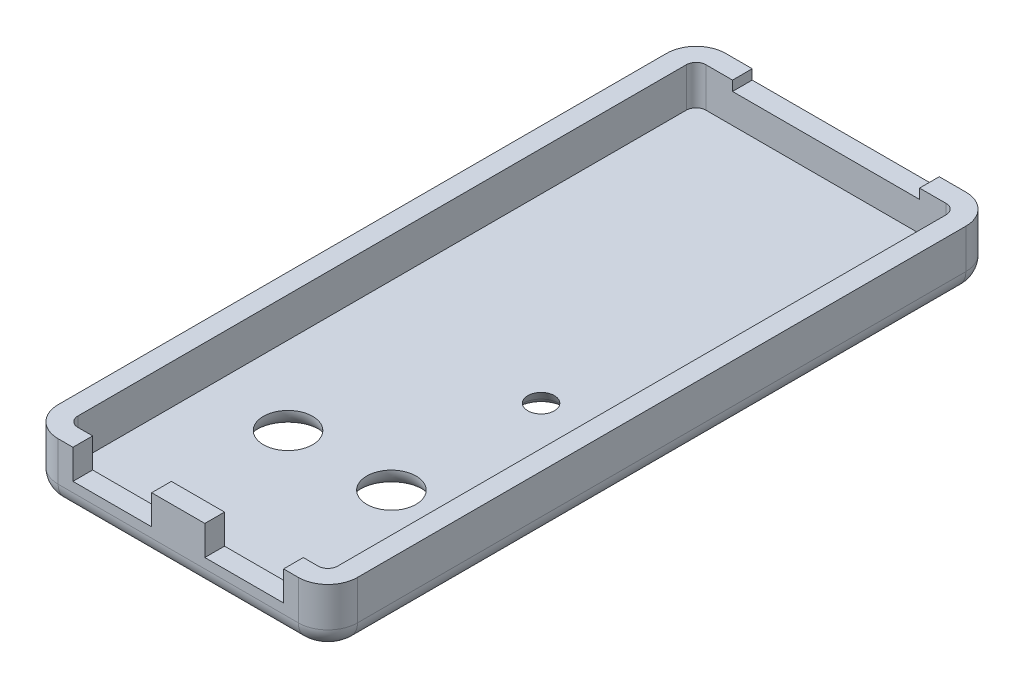
SolidWorks part; units mm, degrees
ref_plane "Front Plane" through (0, 0, 0) normal (0, 0, 1) x (1, 0, 0)
ref_plane "Top Plane" through (0, 0, 0) normal (0, 1, 0) x (1, 0, 0)
ref_plane "Right Plane" through (0, 0, 0) normal (1, 0, 0) x (0, 0, -1)
sketch "Sketch1" plane through (0, 0, 0) normal (0, 1, 0) x (1, 0, 0)
  line L1 (-12.2, 33.9) -> (12.2, 33.9)
  line L2 (-15.2, 30.9) -> (-15.2, -30.9)
  line L3 (-12.2, -33.9) -> (12.2, -33.9)
  line L4 (15.2, 30.9) -> (15.2, -30.9)
  line L5 (-15.2, 33.9) -> (15.2, -33.9) construction
  line L6 (-15.2, -33.9) -> (15.2, 33.9) construction
  arc A0 (-15.2, -30.9) -> (-12.2, -33.9) centre (-12.2, -30.9) ccw
  arc A1 (12.2, -33.9) -> (15.2, -30.9) centre (12.2, -30.9) ccw
  arc A2 (12.2, 33.9) -> (15.2, 30.9) centre (12.2, 30.9) cw
  arc A3 (-12.2, 33.9) -> (-15.2, 30.9) centre (-12.2, 30.9) ccw
  point P0 (0, 0)
  dimension "D3" = 3
  dimension "D1" = 67.8
  dimension "D2" = 30.4
extrude "Boss-Extrude1" add sketch "Sketch1" along normal blind 2
sketch "Sketch2" plane through (0, 2, 0) normal (0, 1, 0) x (1, 0, 0)
  line L0 (-12.2, -31.9) -> (12.2, -31.9)
  line L1 (13.2, -30.9) -> (13.2, 30.9)
  line L2 (12.2, 31.9) -> (-12.2, 31.9)
  line L3 (-13.2, 30.9) -> (-13.2, -30.9)
  line L4 (-12.2, -33.9) -> (12.2, -33.9)
  line L5 (15.2, -30.9) -> (15.2, 30.9)
  line L6 (12.2, 33.9) -> (-12.2, 33.9)
  line L7 (-15.2, 30.9) -> (-15.2, -30.9)
  line L8 (-12.2, -33.9) -> (12.2, -33.9)
  line L9 (15.2, -30.9) -> (15.2, 30.9)
  line L10 (12.2, 33.9) -> (-12.2, 33.9)
  line L11 (-15.2, 30.9) -> (-15.2, -30.9)
  arc A0 (-13.2, -30.9) -> (-12.2, -31.9) centre (-12.2, -30.9) ccw
  arc A1 (12.2, -31.9) -> (13.2, -30.9) centre (12.2, -30.9) ccw
  arc A2 (13.2, 30.9) -> (12.2, 31.9) centre (12.2, 30.9) ccw
  arc A3 (-12.2, 31.9) -> (-13.2, 30.9) centre (-12.2, 30.9) ccw
  arc A4 (-15.2, -30.9) -> (-12.2, -33.9) centre (-12.2, -30.9) ccw
  arc A5 (12.2, -33.9) -> (15.2, -30.9) centre (12.2, -30.9) ccw
  arc A6 (15.2, 30.9) -> (12.2, 33.9) centre (12.2, 30.9) ccw
  arc A7 (-12.2, 33.9) -> (-15.2, 30.9) centre (-12.2, 30.9) ccw
  arc A8 (-15.2, -30.9) -> (-12.2, -33.9) centre (-12.2, -30.9) ccw
  arc A9 (12.2, -33.9) -> (15.2, -30.9) centre (12.2, -30.9) ccw
  arc A10 (15.2, 30.9) -> (12.2, 33.9) centre (12.2, 30.9) ccw
  arc A11 (-12.2, 33.9) -> (-15.2, 30.9) centre (-12.2, 30.9) ccw
  dimension "D1" = 0
  dimension "D2" = 2
extrude "Boss-Extrude2" add sketch "Sketch2" along normal blind 4 separate body
sketch "Sketch3" plane through (0, 0, 33.9) normal (0, 0, 1) x (1, 0, 0)
  line L0 (0, 0) -> (0, 5.6854) construction
  line L1 (10.7, 6) -> (2.7, 6)
  line L2 (10.7, 6) -> (10.7, 3)
  line L3 (10.7, 3) -> (2.7, 3)
  line L4 (2.7, 6) -> (2.7, 3)
  line L5 (10.7, 6) -> (2.7, 3) construction
  line L6 (10.7, 3) -> (2.7, 6) construction
  line L7 (-12.2, 6) -> (12.2, 6) construction
  line L10 (-10.7, 6) -> (-2.7, 6)
  line L11 (-10.7, 6) -> (-10.7, 3)
  line L12 (-10.7, 3) -> (-2.7, 3)
  line L13 (-2.7, 6) -> (-2.7, 3)
  point P0 (6.7, 4.5)
  dimension "D1" = 3
  dimension "D2" = 8
  dimension "D3" = 6.7
extrude "Cut-Extrude1" cut sketch "Sketch3" against normal blind 10
sketch "Sketch4" plane through (0, 0, -33.9) normal (0, 0, -1) x (-1, 0, 0)
  line L0 (-12.2, 6) -> (12.2, 6) construction
  line L1 (9.5, 6) -> (-9.5, 6)
  line L2 (9.5, 6) -> (9.5, 5)
  line L3 (9.5, 5) -> (-9.5, 5)
  line L4 (-9.5, 6) -> (-9.5, 5)
  line L5 (0, 0) -> (0, 5) construction
  dimension "D1" = 19
  dimension "D2" = 1
extrude "Cut-Extrude2" cut sketch "Sketch4" against normal blind 10
sketch "Sketch5" plane through (0, 0, 0) normal (0, -1, 0) x (1, 0, 0)
  circle A0 centre (5.2, 2.245) radius 2.5
extrude "Cut-Extrude3" cut sketch "Sketch5" against normal blind 2 draft 30
sketch "Sketch6" plane through (0, 0, 0) normal (0, -1, 0) x (1, 0, 0)
  line L0 (5.25, 17.5) -> (-5.25, 17.5) construction
  line L1 (0, 17.5) -> (0, 0) construction
  circle A0 centre (5.25, 17.5) radius 2.5
  circle A1 centre (-5.25, 17.5) radius 2.5
  dimension "D2" = 5
  dimension "D1" = 10.5
  dimension "D3" = 17.5
extrude "Cut-Extrude4" cut sketch "Sketch6" against normal up to next (2 mm away)
fillet "Fillet1" radius 2 11 edges at (0, 0, 33.9) (14.3213, 0, 33.0213) (15.2, 0, 0) (14.3213, 0, -33.0213) (0, 0, -33.9) (-14.3213, 0, -33.0213) (-15.2, 0, 0) (-14.3213, 0, 33.0213) (5.2, 0, -0.255) (-5.25, 0, 15) (5.25, 0, 15)
equation "\"D2@Sketch1\"=6.6 + 19.8 + 4"
equation "\"D1@Sketch1\"= 63.80mm + 4"
